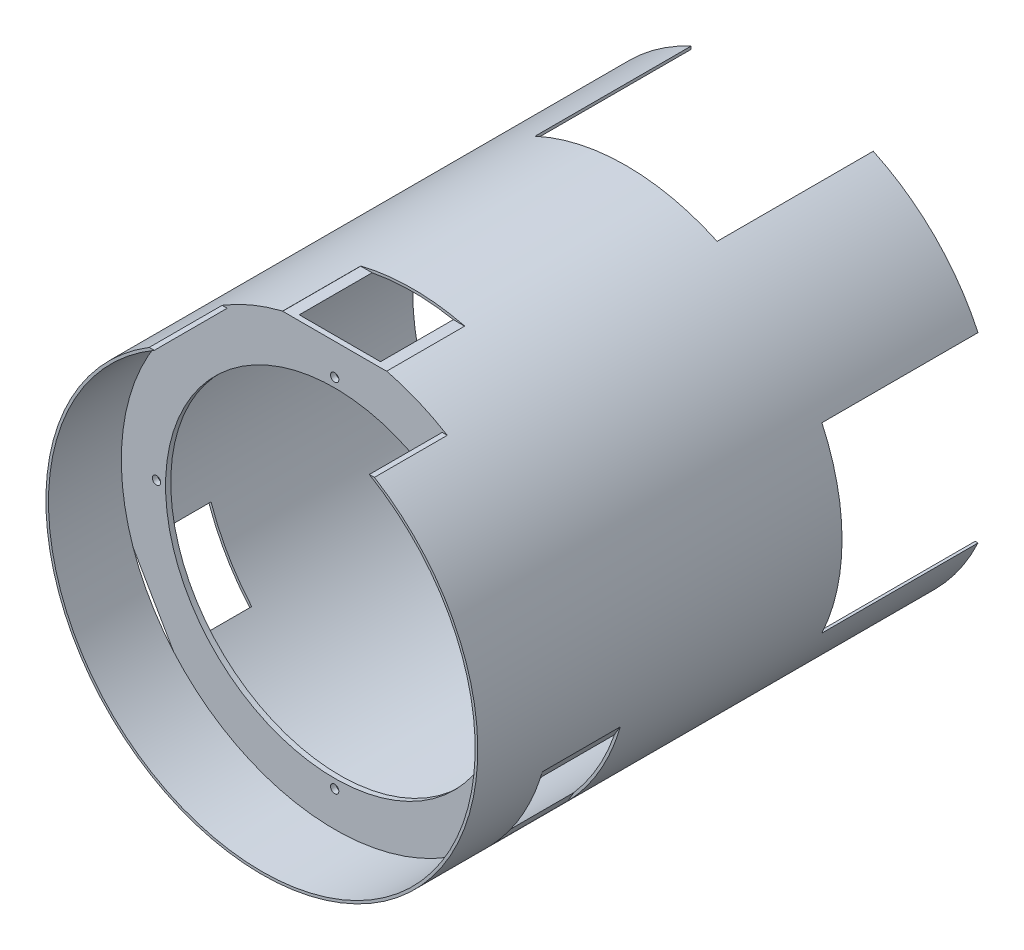
SolidWorks part; units mm, degrees
material "ABS"
ref_plane "前视基准面" through (0, 0, 0) normal (0, 0, 1) x (1, 0, 0)
ref_plane "上视基准面" through (0, 0, 0) normal (0, 1, 0) x (1, 0, 0)
ref_plane "右视基准面" through (0, 0, 0) normal (1, 0, 0) x (0, 0, -1)
sketch "草图1" plane through (0, 0, 0) normal (0, 0, 1) x (1, 0, 0)
  circle A0 centre (0, 0) radius 83
  dimension "D1" = 166
extrude "凸台-拉伸1" add sketch "草图1" along normal blind 100 and the other way blind 100
shell "抽壳1" thickness 1 removed face at (83, 0, -100) removed face at (83, 0, 100)
ref_plane "基准面1" through (0, 0, 70) normal (0, 0, 1) x (1, 0, 0)
sketch "草图2" plane through (0, 0, 70) normal (0, 0, 1) x (1, 0, 0)
  circle A0 centre (0, 0) radius 82.5
  circle A1 centre (0, 0) radius 65
  dimension "D1" = 165
  dimension "D2" = 130
extrude "凸台-拉伸2" add sketch "草图2" along normal blind 2
sketch "草图3" plane through (0, 0, 100) normal (0, 0, 1) x (1, 0, 0)
  line L0 (0, 0) -> (0, 116.4423) construction
  line L1 (43.2734, 70.8267) -> (-43.2734, 70.8267)
  circle A0 centre (0, 0) radius 83 construction
  arc A1 (43.2734, 70.8267) -> (-43.2734, 70.8267) centre (0, 0) ccw
  point P10 (0, 70.8267)
extrude "切除-拉伸1" cut sketch "草图3" against normal up to surface (28 mm away) up to face at (65, 0, 72)
sketch "草图5" plane through (0, 0, 0) normal (0, 1, 0) x (1, 0, 0)
  line L0 (0, 0) -> (0, 70) construction
  line L1 (35, 40) -> (-35, 40)
  line L2 (35, 40) -> (35, 100)
  line L3 (35, 100) -> (-35, 100)
  line L4 (-35, 40) -> (-35, 100)
  line L5 (35, 40) -> (-35, 100) construction
  line L6 (35, 100) -> (-35, 40) construction
  point P0 (0, 70)
  dimension "D1" = 60
  dimension "D2" = 40
  dimension "D3" = 70
extrude "切除-拉伸2" cut sketch "草图5" against normal through all and the other way through all
pattern_circular "阵列(圆周)1" count 4 over 360 about axis through (0, 0, -100) along (0, 0, 1) of "切除-拉伸2"
sketch "草图6" plane through (0, 0, 72) normal (0, 0, -1) x (1, 0, 0)
  line L0 (-64.0452, 60.0705) -> (-84.0452, 25.4295)
  line L1 (-20, -85.5) -> (20, -85.5)
  line L2 (-20, -85.5) -> (-20, -80.5)
  line L3 (-20, -80.5) -> (20, -80.5)
  line L4 (20, -85.5) -> (20, -80.5)
  line L5 (-20, -85.5) -> (20, -80.5) construction
  line L6 (-20, -80.5) -> (20, -85.5) construction
  line L7 (-64.0452, 60.0705) -> (-59.715, 57.5705)
  line L8 (-59.715, 57.5705) -> (-79.715, 22.9295)
  line L9 (-84.0452, 25.4295) -> (-79.715, 22.9295)
  line L10 (-64.0452, 60.0705) -> (-79.715, 22.9295) construction
  line L11 (-59.715, 57.5705) -> (-84.0452, 25.4295) construction
  line L12 (84.0452, 25.4295) -> (64.0452, 60.0705)
  line L13 (84.0452, 25.4295) -> (79.715, 22.9295)
  line L14 (79.715, 22.9295) -> (59.715, 57.5705)
  line L15 (64.0452, 60.0705) -> (59.715, 57.5705)
  line L16 (84.0452, 25.4295) -> (59.715, 57.5705) construction
  line L17 (79.715, 22.9295) -> (64.0452, 60.0705) construction
  arc A0 (-43.2734, -70.8267) -> (43.2734, -70.8267) centre (0, 0) ccw construction
  point P0 (0, -83)
  point P11 (-71.8801, 41.5)
  point P16 (71.8801, 41.5)
  dimension "D1" = 40
  dimension "D2" = 5
  dimension "D3" = 3
extrude "切除-拉伸3" cut sketch "草图6" along normal blind 30
sketch "草图7" plane through (0, 0, 72) normal (0, 0, 1) x (1, 0, 0)
  line L0 (0, 0) -> (0, -68.5) construction
  line L1 (0, 0) -> (68.5, 0) construction
  line L2 (0, 0) -> (-68.5, 0) construction
  line L3 (0, 68.5) -> (0, 0) construction
  circle A0 centre (0, 68.5) radius 1.6
  circle A1 centre (-68.5, 0) radius 1.6
  circle A2 centre (0, -68.5) radius 1.6
  circle A3 centre (68.5, 0) radius 1.6
  circle A4 centre (0, 0) radius 68.5 construction
  dimension "D1" = 137
  dimension "D2" = 3.2
  dimension "D3" = 3.2
  dimension "D4" = 3.2
  dimension "D5" = 3.2
extrude "切除-拉伸4" cut sketch "草图7" against normal up to next
